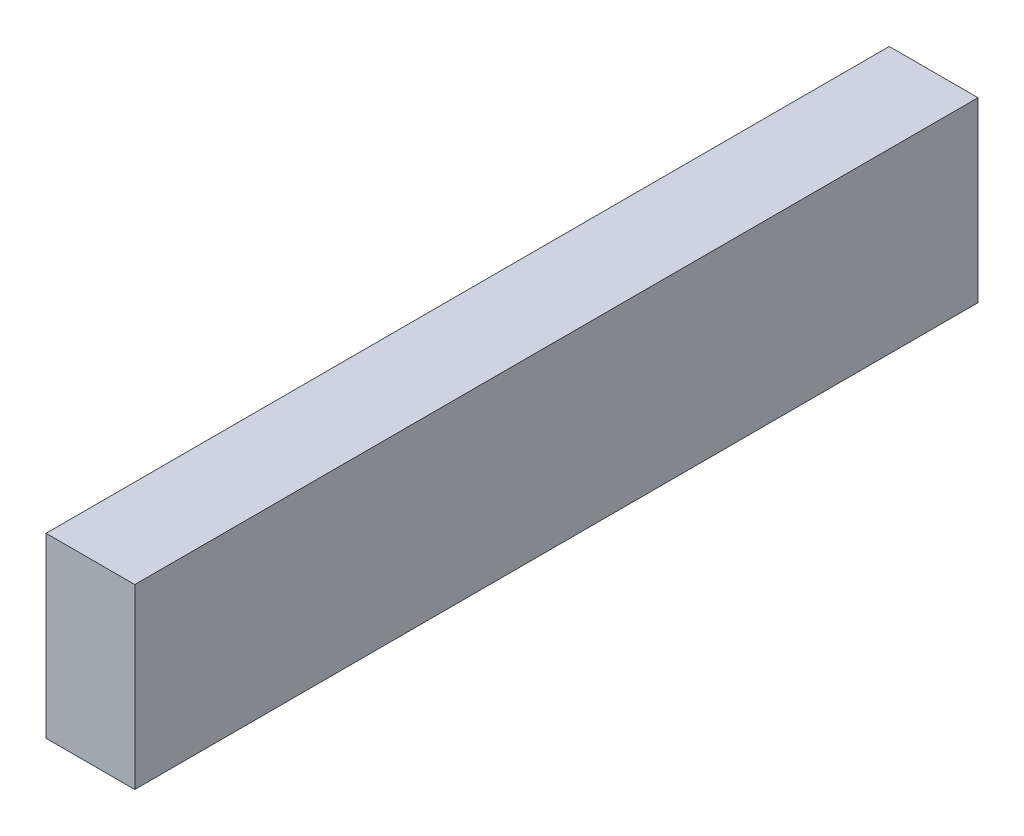
SolidWorks part; units mm, degrees
ref_plane "Front Plane" through (0, 0, 0) normal (0, 0, 1) x (1, 0, 0)
ref_plane "Top Plane" through (0, 0, 0) normal (0, 1, 0) x (1, 0, 0)
ref_plane "Right Plane" through (0, 0, 0) normal (1, 0, 0) x (0, 0, -1)
sketch "Sketch1" plane through (0, 0, 0) normal (0, 0, 1) x (1, 0, 0)
  line L1 (230, 40) -> (210, 40)
  line L2 (230, 40) -> (230, 0)
  line L3 (230, 0) -> (210, 0)
  line L4 (210, 40) -> (210, 0)
  dimension "D1" = 20
extrude "Boss-Extrude1" add sketch "Sketch1" along normal blind 190
